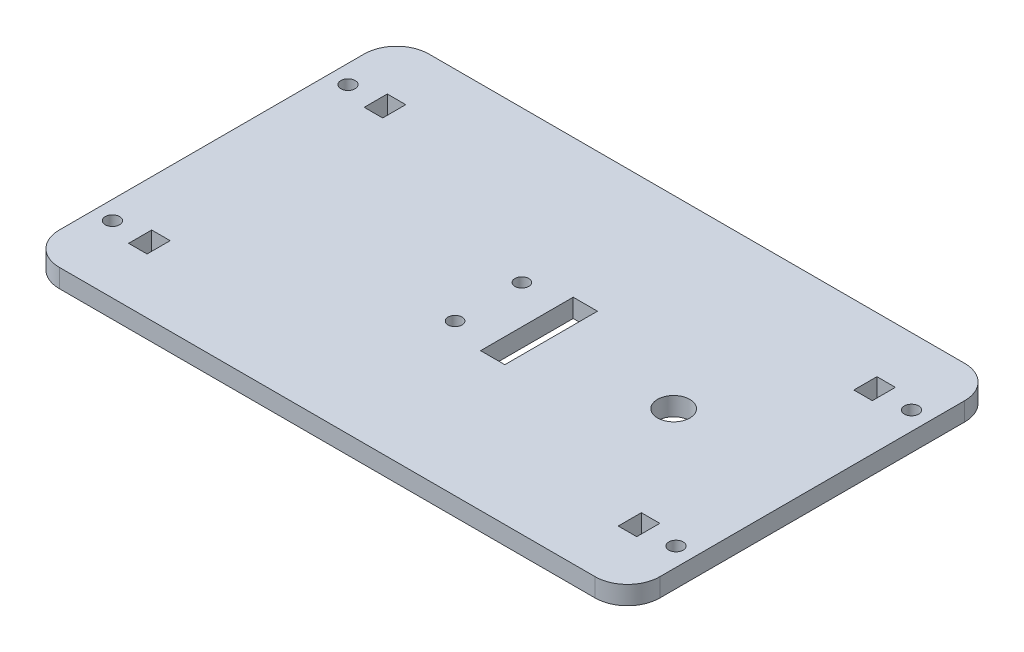
SolidWorks part; units mm, degrees
ref_plane "Front Plane" through (0, 0, 0) normal (0, 0, 1) x (1, 0, 0)
ref_plane "Top Plane" through (0, 0, 0) normal (0, 1, 0) x (1, 0, 0)
ref_plane "Right Plane" through (0, 0, 0) normal (1, 0, 0) x (0, 0, -1)
sketch "Sketch1" plane through (0, 0, 0) normal (0, 1, 0) x (1, 0, 0)
  line L0 (0, 0) -> (0, 18.9717) construction
  line L1 (-58, -40) -> (58, -40)
  line L2 (-65, -33) -> (-65, 33)
  line L3 (-58, 40) -> (58, 40)
  line L4 (65, -33) -> (65, 33)
  line L5 (-65, -40) -> (65, 40) construction
  line L6 (-65, 40) -> (65, -40) construction
  line L11 (0, 0) -> (21.4077, 0) construction
  line L24 (-7.85, 10.0275) -> (7.85, 10.0275) construction
  line L25 (3.2223, 10.0275) -> (8.4756, 10.0275)
  line L26 (3.2223, 10.0275) -> (3.2223, -10.0275)
  line L27 (3.2223, -10.0275) -> (8.4756, -10.0275)
  line L28 (8.4756, 10.0275) -> (8.4756, -10.0275)
  line L30 (51, -23) -> (55, -23)
  line L31 (51, -23) -> (51, -28)
  line L32 (51, -28) -> (55, -28)
  line L33 (55, -23) -> (55, -28)
  line L34 (51, -23) -> (55, -28) construction
  line L35 (51, -28) -> (55, -23) construction
  line L36 (51, 28) -> (55, 28)
  line L37 (51, 28) -> (51, 23)
  line L38 (51, 23) -> (55, 23)
  line L39 (55, 28) -> (55, 23)
  line L40 (51, 28) -> (55, 23) construction
  line L41 (51, 23) -> (55, 28) construction
  line L42 (-55, 28) -> (-51, 28)
  line L43 (-55, 28) -> (-55, 23)
  line L44 (-55, 23) -> (-51, 23)
  line L45 (-51, 28) -> (-51, 23)
  line L46 (-55, 28) -> (-51, 23) construction
  line L47 (-55, 23) -> (-51, 28) construction
  line L48 (-55, -23) -> (-51, -23)
  line L49 (-55, -23) -> (-55, -28)
  line L50 (-55, -28) -> (-51, -28)
  line L51 (-51, -23) -> (-51, -28)
  line L52 (-55, -23) -> (-51, -28) construction
  line L53 (-55, -28) -> (-51, -23) construction
  circle A0 centre (61, 25.5) radius 1.55
  circle A1 centre (61, -25.5) radius 1.55
  circle A2 centre (-61, -25.5) radius 1.55
  circle A3 centre (-61, 25.5) radius 1.55
  circle A4 centre (-5.1, -7.2275) radius 1.5
  circle A5 centre (-5.1, -7.2275) radius 1.5 construction
  circle A6 centre (-5.1, 7.2275) radius 1.5
  circle A7 centre (-5.1, 7.2275) radius 1.5 construction
  circle A8 centre (35, 0) radius 3.5
  arc A9 (58, 40) -> (65, 33) centre (58, 33) cw
  arc A10 (58, -40) -> (65, -33) centre (58, -33) ccw
  arc A11 (-58, -40) -> (-65, -33) centre (-58, -33) cw
  arc A12 (-65, 33) -> (-58, 40) centre (-58, 33) cw
  point P0 (0, 0)
  point P6 (53, 25.5)
  point P14 (-53, 25.5)
  point P19 (-53, -25.5)
  point P48 (3.2223, 0)
  point P62 (53, -25.5)
  dimension "D8" = 3.1
  dimension "D12" = 7
  dimension "D13" = 7
  dimension "D3" = 4
  dimension "D1" = 80
  dimension "D2" = 130
  dimension "D4" = 10
  dimension "D5" = 12
  dimension "D6" = 4
  dimension "D7" = 14.5
  dimension "D9" = 3.2223
  dimension "D10" = 5.2533
  dimension "D11" = 35
  dimension "D14" = 4
  dimension "D15" = 5
  dimension "D16" = 10
  dimension "D17" = 12
  dimension "D18" = 5
  dimension "D19" = 12
  dimension "D20" = 10
  dimension "D21" = 12
  dimension "D22" = 10
extrude "Boss-Extrude1" add sketch "Sketch1" along normal blind 4
